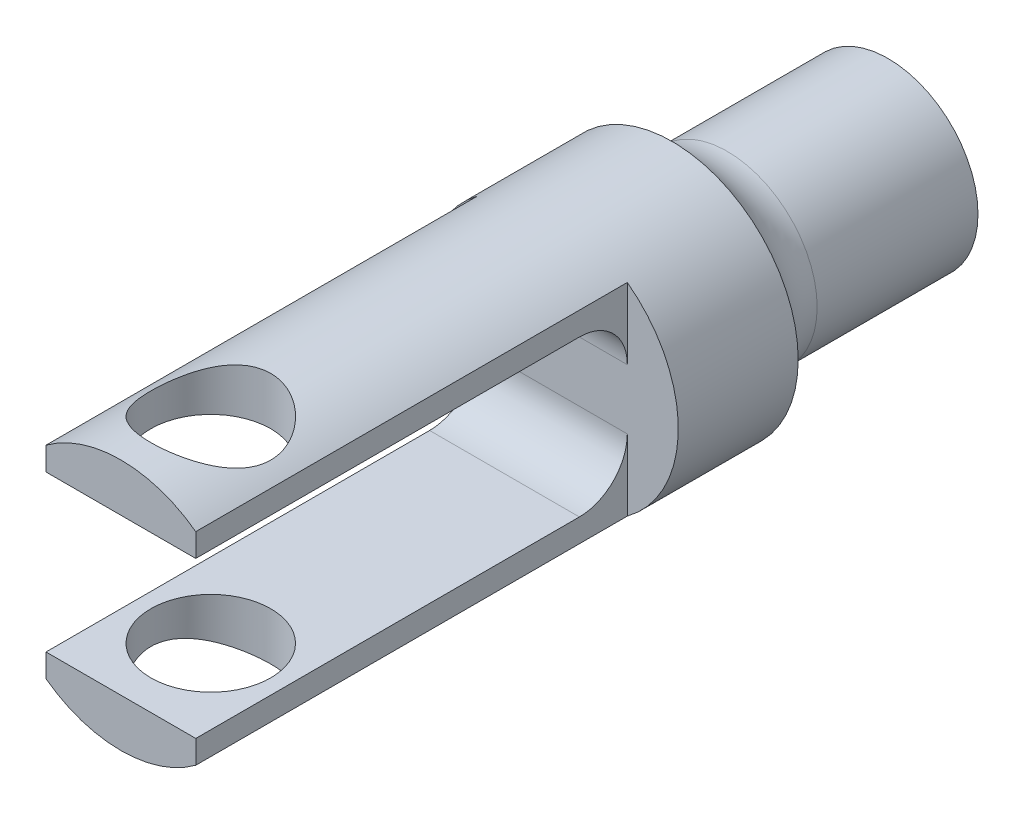
SolidWorks part; units mm, degrees
ref_plane "Płaszczyzna przednia" through (0, 0, 0) normal (0, 0, 1) x (1, 0, 0)
ref_plane "Płaszczyzna górna" through (0, 0, 0) normal (0, 1, 0) x (1, 0, 0)
ref_plane "Płaszczyzna prawa" through (0, 0, 0) normal (1, 0, 0) x (0, 0, -1)
sketch "Szkic1" plane through (0, 0, 0) normal (0, 0, 1) x (1, 0, 0)
  line L1 (-2.39, 12.465) -> (2.39, 12.465)
  line L2 (-2.39, 12.465) -> (-2.39, 8.465)
  line L3 (-2.39, 8.465) -> (2.39, 8.465)
  line L4 (2.39, 12.465) -> (2.39, 8.465)
  circle A0 centre (0, 0) radius 11.115
  circle A1 centre (0, 0) radius 15
  point P8 (0, 8.465)
  dimension "D1" = 22.23
  dimension "D2" = 30
  dimension "D3" = 4.78
  dimension "D4" = 8.465
  dimension "D5" = 4
extrude "Dodanie-wyciągnięcie1" add sketch "Szkic1" along normal blind 36 contours A1 A0 L2 L1 L4 region at (-14.5757, 0, 0)
sketch "Szkic3" plane through (0, 0, 36) normal (0, 0, 1) x (1, 0, 0)
  circle A0 centre (0, 0) radius 11.115
  circle A3 centre (0, 0) radius 21
  dimension "D1" = 22.23
  dimension "D2" = 42
extrude "Dodanie-wyciągnięcie2" add sketch "Szkic3" along normal blind 20
sketch "Szkic5" plane through (0, 0, 56) normal (0, 0, 1) x (1, 0, 0)
  circle A0 centre (0, 0) radius 11.115 construction
  circle A1 centre (0, 0) radius 11.115
extrude "Dodanie-wyciągnięcie4" add sketch "Szkic5" against normal blind 17
fillet "Zaokrąglenie1" radius 10 1 edges at (15, 0, 36)
sketch "Szkic4" plane through (0, 0, 56) normal (0, 0, 1) x (1, 0, 0)
  line L0 (-16.4924, 13) -> (16.4924, 13)
  line L1 (-16.4924, -13) -> (16.4924, -13)
  line L2 (-12.4924, 16.8801) -> (-12.4924, 13)
  line L3 (12.4924, 16.8801) -> (12.4924, 13)
  line L4 (-12.4924, -13) -> (-12.4924, -16.8801)
  line L5 (12.4924, -13) -> (12.4924, -16.8801)
  circle A0 centre (0, 0) radius 21 construction
  arc A1 (-16.4924, -13) -> (16.4924, -13) centre (0, 0) ccw
  arc A2 (16.4924, 13) -> (-16.4924, 13) centre (0, 0) ccw
  circle M3 centre (0, 0) radius 21
  dimension "D1" = 13
  dimension "D2" = 13
  dimension "D3" = 4
  dimension "D4" = 4
  dimension "D5" = 4
extrude "Dodanie-wyciągnięcie3" add sketch "Szkic4" along normal blind 72 contours L3 L2 L0 M3 | L5 L1 L4 M3 region at (0, 16.4519, 56) region at (0, -16.4519, 56)
fillet "Zaokrąglenie2" radius 8 2 edges at (0, -13, 56) (0, 13, 56)
sketch "Szkic6" plane through (0, -13, 0) normal (0, 1, 0) x (1, 0, 0)
  line L2 (-12.4924, -128) -> (12.4924, -128) construction
  circle A0 centre (0, -113) radius 10
  point P4 (0, -128)
  dimension "D1" = 20
  dimension "D2" = 15
extrude "Wytnij-wyciągnięcie1" cut sketch "Szkic6" against normal up to next and the other way through all
